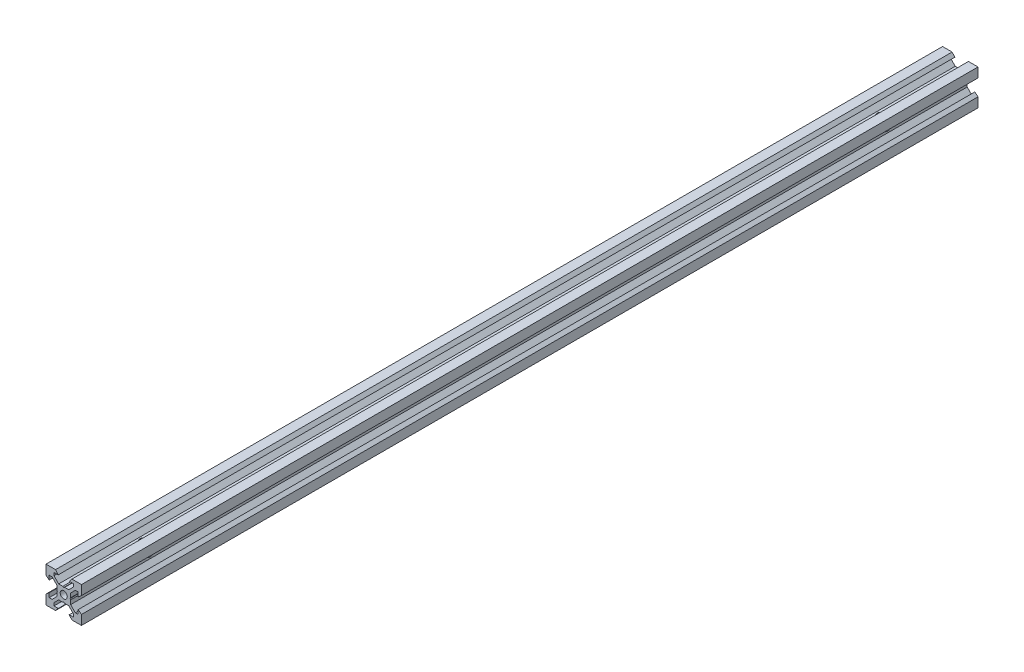
SolidWorks part; units mm, degrees
material "3.3535 (EN-AW 5754)"
ref_plane "Front Plane" through (0, 0, 0) normal (0, 0, 1) x (1, 0, 0)
ref_plane "Top Plane" through (0, 0, 0) normal (0, 1, 0) x (1, 0, 0)
ref_plane "Right Plane" through (0, 0, 0) normal (1, 0, 0) x (0, 0, -1)
sketch "Sketch1" plane through (0, 0, 0) normal (0, 0, 1) x (1, 0, 0)
  line L0 (10, 10) -> (4.6104, 10) construction
  line L1 (10, 10) -> (10, 4.6104) construction
  line L2 (10, -10) -> (10, -4.6104) construction
  line L3 (10, -10) -> (4.6104, -10) construction
  line L4 (10, 10) -> (10, 4.6104)
  line L5 (6.5607, 5.5) -> (8.2, 5.5)
  line L6 (5.5, 8.2) -> (5.5, 6.5607)
  line L7 (10, 10) -> (4.6104, 10)
  line L8 (10, 10) -> (10, 4.6104)
  line L9 (6.5607, 5.5) -> (3.9, 2.8393)
  line L10 (5.5, 6.5607) -> (2.8393, 3.9)
  line L11 (10, 4.6104) -> (8.2, 3.1)
  line L12 (4.6104, 10) -> (3.1, 8.2)
  line L13 (8.2, 3.1) -> (8.2, 5.5)
  line L14 (3.1, 8.2) -> (5.5, 8.2)
  line L15 (-6.5607, 5.5) -> (-8.2, 5.5)
  line L16 (6.5607, -5.5) -> (8.2, -5.5)
  line L17 (3.1, -8.2) -> (5.5, -8.2)
  line L18 (8.2, -3.1) -> (8.2, -5.5)
  line L19 (4.6104, -10) -> (3.1, -8.2)
  line L20 (10, -4.6104) -> (8.2, -3.1)
  line L21 (0.5196, -3.9) -> (0, -3.6)
  line L22 (0.5196, 3.9) -> (0, 3.6)
  line L23 (3.6, 0) -> (3.9, -0.5196)
  line L24 (3.9, 0.5196) -> (3.6, 0)
  line L25 (3.9, 0.5196) -> (3.9, 2.8393)
  line L26 (2.8393, 3.9) -> (0.5196, 3.9)
  line L27 (3.9, -2.8393) -> (3.9, -0.5196)
  line L28 (2.8393, -3.9) -> (0.5196, -3.9)
  line L29 (5.5, -6.5607) -> (2.8393, -3.9)
  line L30 (6.5607, -5.5) -> (3.9, -2.8393)
  line L31 (10, -10) -> (10, -4.6104)
  line L32 (10, -10) -> (4.6104, -10)
  line L33 (5.5, -8.2) -> (5.5, -6.5607)
  line L34 (-6.5607, -5.5) -> (-8.2, -5.5)
  line L35 (10, -10) -> (10, -4.6104)
  line L36 (0, 0) -> (0, 8.2) construction
  line L37 (-10, -10) -> (-4.6104, -10) construction
  line L38 (-10, -10) -> (-10, -4.6104) construction
  line L39 (-10, 10) -> (-10, 4.6104) construction
  line L40 (-10, 10) -> (-4.6104, 10) construction
  line L41 (-10, -10) -> (-10, -4.6104)
  line L43 (-5.5, -8.2) -> (-5.5, -6.5607)
  line L44 (-10, -10) -> (-4.6104, -10)
  line L45 (-10, -10) -> (-10, -4.6104)
  line L46 (-6.5607, -5.5) -> (-3.9, -2.8393)
  line L47 (-5.5, -6.5607) -> (-2.8393, -3.9)
  line L48 (-2.8393, -3.9) -> (-0.5196, -3.9)
  line L49 (-3.9, -2.8393) -> (-3.9, -0.5196)
  line L50 (-2.8393, 3.9) -> (-0.5196, 3.9)
  line L51 (-3.9, 0.5196) -> (-3.9, 2.8393)
  line L52 (-3.9, 0.5196) -> (-3.6, 0)
  line L53 (-3.6, 0) -> (-3.9, -0.5196)
  line L54 (-0.5196, 3.9) -> (0, 3.6)
  line L55 (-0.5196, -3.9) -> (0, -3.6)
  line L56 (-10, -4.6104) -> (-8.2, -3.1)
  line L57 (-4.6104, -10) -> (-3.1, -8.2)
  line L58 (-8.2, -3.1) -> (-8.2, -5.5)
  line L59 (-3.1, -8.2) -> (-5.5, -8.2)
  line L60 (-10, -10) -> (10, -10) construction
  line L61 (-10, -10) -> (-10, 10) construction
  line L62 (-3.1, 8.2) -> (-5.5, 8.2)
  line L63 (-8.2, 3.1) -> (-8.2, 5.5)
  line L64 (-4.6104, 10) -> (-3.1, 8.2)
  line L65 (-10, 4.6104) -> (-8.2, 3.1)
  line L66 (-5.5, 6.5607) -> (-2.8393, 3.9)
  line L67 (-6.5607, 5.5) -> (-3.9, 2.8393)
  line L68 (-10, 10) -> (-10, 4.6104)
  line L69 (-10, 10) -> (-4.6104, 10)
  line L70 (-5.5, 8.2) -> (-5.5, 6.5607)
  line L71 (-10, 10) -> (10, 10) construction
  line L72 (-10, 10) -> (-10, 4.6104)
  line L73 (10, -10) -> (10, 10) construction
  line L74 (-10, -10) -> (10, 10) construction
  line L75 (-10, 10) -> (10, -10) construction
  circle A0 centre (0, 0) radius 2
  dimension "D7" = 4
  dimension "D1" = 20
  dimension "D2" = 5.3896
  dimension "D3" = 4.5
  dimension "D4" = 50
  dimension "D5" = 1.8
  dimension "D6" = 1.5104
  dimension "D8" = 5.5
  dimension "D9" = 120
  dimension "D10" = 0.3
  dimension "D11" = 2.3197
  dimension "D12" = 7.8
  dimension "D13" = 7.8
  dimension "D14" = 1.5
  dimension "D15" = 2.6607
extrude "Boss-Extrude1" add sketch "Sketch1" along normal blind 506 contours L70 L62 L64 L69 L68 L65 L63 L15 L67 L51 L52 L53 L49 L46 L34 L58 L56 L41 L44 L57 L59 L43 L47 L48 L55 L21 L28 L29 L33 L17 L19 L32 L31 L20 L18 L16 L30 L27 L23 L24 L25 L9 L5 L13 L11 L4 L7 L12 L14 L6 L10 region at (9.7172, 7.3052, 0)
sketch "Sketch2" plane through (0, -3.9, 0) normal (0, -1, 0) x (-1, 0, 0)
  line L0 (0, -506) -> (0, -461) construction
  line L1 (0, -506) -> (0, 0) construction
  line L2 (0, 0) -> (0, -45) construction
  circle A0 centre (0, -461) radius 2
  circle A1 centre (0, -45) radius 2
  dimension "D2" = 4
  dimension "D4" = 4
  dimension "D1" = 45
  dimension "D3" = 45
extrude "Cut-Extrude1" cut sketch "Sketch2" against normal through all both and the other way through all
sketch "Sketch3" plane through (3.9, 0, 0) normal (1, 0, 0) x (0, 0, -1)
  line L0 (0, 0) -> (-45, 0) construction
  line L1 (-506, 0) -> (0, 0) construction
  line L2 (-506, 0) -> (-461, 0) construction
  circle A0 centre (-45, 0) radius 2
  circle A1 centre (-461, 0) radius 2
  dimension "D2" = 4
  dimension "D4" = 4
  dimension "D1" = 45
  dimension "D3" = 45
extrude "Cut-Extrude2" cut sketch "Sketch3" against normal through all both
